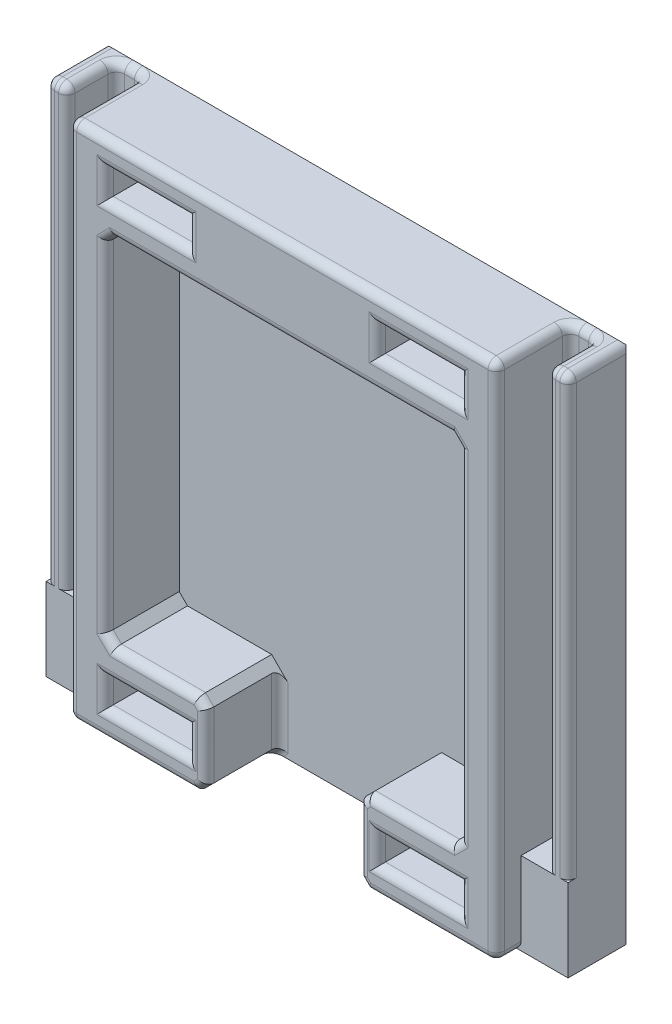
SolidWorks part; units mm, degrees
ref_plane "Plan de face" through (0, 0, 0) normal (0, 0, 1) x (1, 0, 0)
ref_plane "Plan de dessus" through (0, 0, 0) normal (0, 1, 0) x (1, 0, 0)
ref_plane "Plan de droite" through (0, 0, 0) normal (1, 0, 0) x (0, 0, -1)
sketch "Esquisse2" plane through (0, 0, 0) normal (0, 0, 1) x (1, 0, 0)
  line L0 (0, -21.5) -> (0, -31.5)
  line L1 (-21.5, -21.5) -> (21.5, -21.5)
  line L2 (-21.5, -21.5) -> (-21.5, 21.5)
  line L3 (-21.5, 21.5) -> (21.5, 21.5)
  line L4 (21.5, -21.5) -> (21.5, 21.5)
  line L5 (-21.5, -21.5) -> (21.5, 21.5) construction
  line L6 (-21.5, 21.5) -> (21.5, -21.5) construction
  line L7 (-25.9306, -31.5) -> (25.9306, -31.5)
  line L8 (-25.9306, -31.5) -> (-25.9306, 31.5)
  line L9 (-25.9306, 31.5) -> (25.9306, 31.5)
  line L10 (25.9306, -31.5) -> (25.9306, 31.5)
  line L11 (-25.9306, -31.5) -> (25.9306, 31.5) construction
  line L12 (-25.9306, 31.5) -> (25.9306, -31.5) construction
  line L13 (9.3, -21.5) -> (9.3, -31.5)
  line L14 (9.3, -21.5) -> (-9.3, -21.5)
  line L15 (0, -21.5) -> (0, -31.5)
  line L16 (9.3, -31.5) -> (-9.3, -31.5)
  line L17 (-9.3, -21.5) -> (-9.3, -31.5)
  point P0 (0, 0)
  point P6 (0, 0)
  dimension "D1" = 43
  dimension "D2" = 43
  dimension "D3" = 10
  dimension "D4" = 9.3
extrude "Boss.-Extru.2" add sketch "Esquisse2" along normal blind 9 contours L17 L1 L2 L3 L4 L13 L7 L10 L9 L8 region at (-10.116, -26.5, 0)
sketch "Esquisse3" plane through (0, 0, 0) normal (0, 0, -1) x (-1, 0, 0)
  line L1 (-25.9306, 31.5) -> (25.9306, 31.5)
  line L2 (-25.9306, 31.5) -> (-25.9306, -31.5)
  line L3 (-25.9306, -31.5) -> (25.9306, -31.5)
  line L4 (25.9306, 31.5) -> (25.9306, -31.5)
extrude "Boss.-Extru.3" add sketch "Esquisse3" along normal blind 3
sketch "Esquisse4" plane through (0, 0, 9) normal (0, 0, 1) x (1, 0, 0)
  line L0 (0, 31.5) -> (0, -31.5)
  line L1 (-25.9306, 31.5) -> (25.9306, 31.5) construction
  line L2 (9.3, -31.5) -> (-9.3, -31.5) construction
  line L3 (-21.5, 21.5) -> (-21.5, 28.3955)
  line L4 (-25.9306, 0) -> (0, 0)
  line L5 (-21.5, 28.3955) -> (-11.5, 28.3955)
  line L6 (-21.5, 28.3955) -> (-21.5, 24.9955)
  line L7 (-21.5, 24.9955) -> (-11.5, 24.9955)
  line L8 (-11.5, 28.3955) -> (-11.5, 24.9955)
  line L9 (-25.9306, -31.5) -> (-25.9306, 31.5) construction
  line L10 (-21.5, -24.9955) -> (-11.5, -24.9955)
  line L11 (-11.5, -28.3955) -> (-11.5, -24.9955)
  line L12 (-21.5, -28.3955) -> (-11.5, -28.3955)
  line L13 (-21.5, -28.3955) -> (-21.5, -24.9955)
  line L14 (21.5, -28.3955) -> (21.5, -24.9955)
  line L15 (21.5, -28.3955) -> (11.5, -28.3955)
  line L16 (11.5, -28.3955) -> (11.5, -24.9955)
  line L17 (21.5, -24.9955) -> (11.5, -24.9955)
  line L18 (21.5, 24.9955) -> (11.5, 24.9955)
  line L19 (11.5, 28.3955) -> (11.5, 24.9955)
  line L20 (21.5, 28.3955) -> (11.5, 28.3955)
  line L21 (21.5, 28.3955) -> (21.5, 24.9955)
  dimension "D1" = 3.4
extrude "Enlèv. mat.-Extru.1" cut sketch "Esquisse4" against normal blind 7 contours L13 L12 L11 L10 | L14 L17 L16 L15 | L18 L19 L20 L21 | L6 L7 L8 L5 region at (-16.5, -26.6955, 9) region at (16.5, -26.6955, 9)
sketch "Esquisse5" plane through (0, 31.5, 0) normal (0, 1, 0) x (1, 0, 0)
  line L0 (0, 3) -> (0, -9)
  line L1 (-25.9306, 3) -> (25.9306, 3) construction
  line L2 (-25.9306, -9) -> (25.9306, -9) construction
  line L3 (25.9306, 0) -> (29.1306, 0)
  line L4 (-25.9306, 3) -> (-29.1306, 3)
  line L5 (-25.9306, 3) -> (-25.9306, 0)
  line L6 (-25.9306, 0) -> (-29.1306, 0)
  line L7 (-29.1306, 3) -> (-29.1306, 0)
  line L8 (-29.1306, 3) -> (-31.6306, 3)
  line L9 (-29.1306, 3) -> (-29.1306, -6)
  line L10 (-29.1306, -6) -> (-31.6306, -6)
  line L11 (-31.6306, 3) -> (-31.6306, -6)
  line L12 (29.1306, 3) -> (29.1306, 0)
  line L13 (25.9306, 3) -> (29.1306, 3)
  line L14 (25.9306, 3) -> (25.9306, 0)
  line L15 (29.1306, -6) -> (31.6306, -6)
  line L16 (31.6306, 3) -> (31.6306, -6)
  line L17 (29.1306, 3) -> (31.6306, 3)
  line L18 (29.1306, 3) -> (29.1306, -6)
  line M10 (25.9306, -9) -> (25.9306, 3)
  line M12 (-25.9306, 3) -> (-25.9306, -9)
  dimension "D1" = 9
  dimension "D2" = 2.5
  dimension "D3" = 3.2
extrude "Boss.-Extru.4" add sketch "Esquisse5" against normal up to surface (63 mm away) contours L8 L11 L10 L9 L7 | L4 L7 L6 M12 | L13 L3 L12 M10 | L12 L18 L15 L16 L17 region at (27.5306, 31.5, -1.5) region at (30.3806, 31.5, 1.5) region at (-27.5306, 31.5, -1.5) region at (-30.3806, 31.5, 1.5) up to face at (0, -31.5, 3.75)
chamfer "Chanfrein1" distance 1 angle 45 4 edges at (-21.5, -21.5, 4.5) (21.5, -21.5, 4.5) (21.5, 21.5, 4.5) (-21.5, 21.5, 4.5)
chamfer "Chanfrein2" distance 2 angle 45 4 edges at (-31.6306, 0, -3) (0, -31.5, -3) (31.6306, 0, -3) (0, 31.5, -3)
fillet "Congé1" radius 1 8 edges at (31.6306, 0, 6) (29.1306, 0, 6) (29.1306, 0, 0) (25.9306, 0, 0) (-29.1306, 0, 6) (-31.6306, 0, 6) (-29.1306, 0, 0) (-25.9306, 0, 0)
fillet "Congé2" radius 1 36 edges at (-31.6306, 31.5, 2) (-31.3377, 31.5, 5.7071) (-30.3806, 31.5, 6) (-29.4235, 31.5, 5.7071) (-29.1306, 31.5, 3) (-28.8377, 31.5, 0.2929) (-27.5306, 31.5, 0) (-26.2235, 31.5, 0.2929) (-31.6306, -31.5, 2) (-31.3377, -31.5, 5.7071) (-30.3806, -31.5, 6) (-29.4235, -31.5, 5.7071) (-29.1306, -31.5, 3) (-28.8377, -31.5, 0.2929) (-27.5306, -31.5, 0) (-26.2235, -31.5, 0.2929) (31.6306, -31.5, 2) (31.3377, -31.5, 5.7071) (30.3806, -31.5, 6) (29.4235, -31.5, 5.7071) (29.1306, -31.5, 3) (28.8377, -31.5, 0.2929) (27.5306, -31.5, 0) (26.2235, -31.5, 0.2929) (31.6306, 31.5, 2) (31.3377, 31.5, 5.7071) (30.3806, 31.5, 6) (29.4235, 31.5, 5.7071) (29.1306, 31.5, 3) (28.8377, 31.5, 0.2929) (27.5306, 31.5, 0) (26.2235, 31.5, 0.2929) (-25.9306, 31.5, 5) (-25.9306, -31.5, 5) (25.9306, -31.5, 5) (25.9306, 31.5, 5)
chamfer "Chanfrein4" distance 1 angle 45 4 edges at (9.3, -31.5, 4.5) (-9.3, -31.5, 4.5) (9.3, -21.5, 4.5) (-9.3, -21.5, 4.5)
fillet "Congé4" radius 1 40 edges at (-16.5, 24.9955, 9) (-11.5, 26.6955, 9) (-16.5, 28.3955, 9) (-21.5, 26.6955, 9) (11.5, 26.6955, 9) (16.5, 24.9955, 9) (21.5, 26.6955, 9) (16.5, 28.3955, 9) (-11.5, -26.6955, 9) (-16.5, -24.9955, 9) (-21.5, -26.6955, 9) (-16.5, -28.3955, 9) (9.8, -22, 9) (15.4, -21.5, 9) (21, -21, 9) (21.5, 0, 9) (21, 21, 9) (0, 21.5, 9) (-21, 21, 9) (-21.5, 0, 9) (-21, -21, 9) (-15.4, -21.5, 9) (-9.8, -22, 9) (-9.3, -26.5, 9) (-9.8, -31, 9) (-17.6153, -31.5, 9) (-25.6377, -31.2071, 9) (-25.9306, 0, 9) (-25.6377, 31.2071, 9) (0, 31.5, 9) (25.6377, 31.2071, 9) (25.9306, 0, 9) (25.6377, -31.2071, 9) (17.6153, -31.5, 9) (9.8, -31, 9) (9.3, -26.5, 9) (16.5, -24.9955, 9) (11.5, -26.6955, 9) (16.5, -28.3955, 9) (21.5, -26.6955, 9)
fillet "Congé5" radius 1 4 edges at (9.8, -31, 0) (9.3, -26.5, 0) (-9.8, -31, 0) (-9.3, -26.5, 0)
sketch "Esquisse6" plane through (0, -31.5, 0) normal (0, -1, 0) x (1, 0, 0)
  line L0 (-26.9306, -1) -> (26.9306, -1) construction
  line L1 (31.6306, 5) -> (24.9271, 5)
  line L2 (31.6306, 5) -> (31.6306, -1)
  line L3 (31.6306, -1) -> (24.9271, -1)
  line L4 (24.9271, 5) -> (24.9271, -1)
  line L5 (0, -1) -> (0, 5)
  line L6 (24.9271, 5) -> (31.6306, 5)
  line L7 (24.9271, 5) -> (24.9271, 6)
  line L8 (24.9271, 6) -> (31.6306, 6)
  line L9 (31.6306, 5) -> (31.6306, 6)
  line L10 (-24.9271, 6) -> (-31.6306, 6)
  line L11 (-31.6306, 5) -> (-31.6306, 6)
  line L12 (-24.9271, 5) -> (-31.6306, 5)
  line L13 (-24.9271, 5) -> (-24.9271, 6)
  line L14 (-31.6306, -1) -> (-24.9271, -1)
  line L15 (-24.9271, 5) -> (-24.9271, -1)
  line L16 (-31.6306, 5) -> (-24.9271, 5)
  line L17 (-31.6306, 5) -> (-31.6306, -1)
  line M14 (-24.9306, 8) -> (-24.9306, 1)
  arc M15 (-24.9306, 1) -> (-26.9306, -1) centre (-26.9306, 1) cw
  arc M17 (26.9306, -1) -> (24.9306, 1) centre (26.9306, 1) cw
  line M18 (24.9306, 1) -> (24.9306, 8)
extrude "Boss.-Extru.5" add sketch "Esquisse6" against normal blind 10 contours L12 L17 L14 M15 M14 | L12 L10 L11 M14 | L3 L2 L1 M18 M17 | L1 L9 L8 M18 region at (28.344, -31.5, 2.0557) region at (28.2806, -31.5, 5.5) region at (-28.2806, -31.5, 5.5) region at (-28.344, -31.5, 2.0557)
